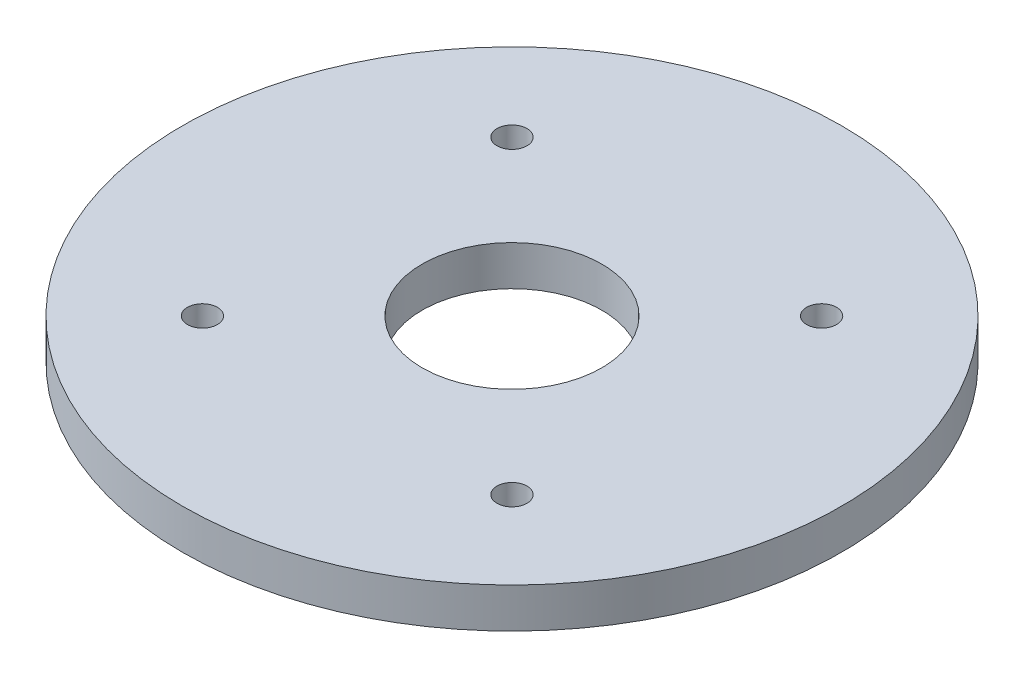
SolidWorks part; units mm, degrees
ref_plane "Front Plane" through (0, 0, 0) normal (0, 0, 1) x (1, 0, 0)
ref_plane "Top Plane" through (0, 0, 0) normal (0, 1, 0) x (1, 0, 0)
ref_plane "Right Plane" through (0, 0, 0) normal (1, 0, 0) x (0, 0, -1)
sketch "Sketch1" plane through (0, 0, 0) normal (0, 1, 0) x (1, 0, 0)
  line L1 (-15.5, 15.5) -> (15.5, 15.5)
  line L2 (-15.5, 15.5) -> (-15.5, -15.5)
  line L3 (-15.5, -15.5) -> (15.5, -15.5)
  line L4 (15.5, 15.5) -> (15.5, -15.5)
  line L5 (-15.5, 15.5) -> (15.5, -15.5) construction
  line L6 (-15.5, -15.5) -> (15.5, 15.5) construction
  circle A0 centre (0, 0) radius 33
  circle A1 centre (-15.5, 15.5) radius 1.5
  circle A2 centre (15.5, 15.5) radius 1.5
  circle A3 centre (-15.5, -15.5) radius 1.5
  circle A4 centre (15.5, -15.5) radius 1.5
  circle A5 centre (0, 0) radius 9
  dimension "D1" = 66
  dimension "D4" = 3
  dimension "D5" = 3
  dimension "D6" = 3
  dimension "D7" = 3
  dimension "D8" = 18
  dimension "D2" = 31
  dimension "D3" = 31
extrude "Boss-Extrude1" add sketch "Sketch1" along normal blind 4 contours A0 A4 L3 A3 L2 A1 L1 A2 L4 | A4 L4 A2 L1 A1 L2 A3 L3 A5 region at (0, 0, -15.0616) region at (-32.0666, 0, 0)
